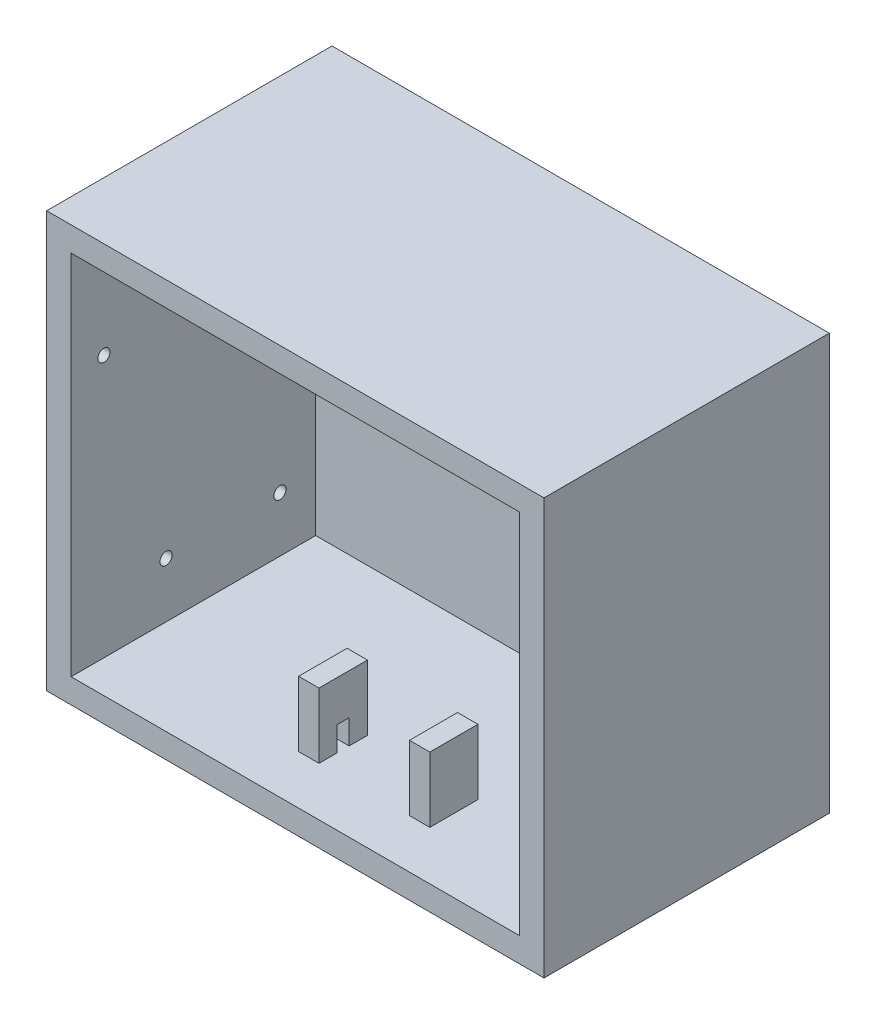
SolidWorks part; units mm, degrees
ref_plane "Front Plane" through (0, 0, 0) normal (0, 0, 1) x (1, 0, 0)
ref_plane "Top Plane" through (0, 0, 0) normal (0, 1, 0) x (1, 0, 0)
ref_plane "Right Plane" through (0, 0, 0) normal (1, 0, 0) x (0, 0, -1)
sketch "Sketch1" plane through (0, 0, 0) normal (0, 0, 1) x (1, 0, 0)
  line L0 (61, 51) -> (-61, 51)
  line L1 (55, -45) -> (-55, -45)
  line L2 (55, -45) -> (55, 45)
  line L3 (55, 45) -> (-55, 45)
  line L4 (-55, -45) -> (-55, 45)
  line L5 (55, -45) -> (-55, 45) construction
  line L6 (55, 45) -> (-55, -45) construction
  line L7 (-61, -51) -> (-61, 51)
  line L8 (61, -51) -> (-61, -51)
  line L9 (61, -51) -> (61, 51)
  point P0 (0, 0)
  dimension "D1" = 90
  dimension "D2" = 110
  dimension "D3" = 6
extrude "Boss-Extrude1" add sketch "Sketch1" along normal blind 70
sketch "Sketch3" plane through (61, 0, 0) normal (1, 0, 0) x (0, 0, -1)
  line L0 (-70, -51) -> (0, -51) construction
  line L1 (0, 51) -> (-10, 51)
  line L2 (0, 51) -> (0, -51)
  line L3 (0, -51) -> (-10, -51)
  line L4 (-10, 51) -> (-10, -51)
  dimension "D1" = 10
extrude "Boss-Extrude3" add sketch "Sketch3" against normal blind 122
sketch "Sketch5" plane through (-61, 0, 0) normal (-1, 0, 0) x (0, 0, 1)
  line L0 (70, 51) -> (0, 51) construction
  line L1 (11.16, 34.5) -> (64.5, 34.5)
  line L2 (11.16, 34.5) -> (11.16, -34.08)
  line L3 (11.16, -34.08) -> (64.5, -34.08)
  line L4 (64.5, 34.5) -> (64.5, -34.08)
  line L5 (70, 51) -> (70, -51) construction
  circle A0 centre (61.96, 19.26) radius 1.5
  circle A1 centre (13.7, 19.26) radius 1.5
  point P4 (37.83, 34.5)
  point P9 (64.5, 19.26)
  point P10 (61.96, 19.26)
  point P11 (13.7, 19.26)
  dimension "D1" = 68.58
  dimension "D2" = 53.34
  dimension "D3" = 16.5
  dimension "D4" = 5.5
  dimension "D5" = 15.24
  dimension "D6" = 2.54
  dimension "D7" = 2.54
sketch "Sketch6" plane through (-61, 0, 0) normal (-1, 0, 0) x (0, 0, 1)
  line L0 (11.16, -34.08) -> (64.5, -34.08) construction
  circle A0 centre (18.78, -31.5) radius 1.5
  circle A1 centre (46.72, -31.5) radius 1.5
  point P0 (18.78, -34.08)
  point P1 (-61.2014, -14.8235)
  point P2 (-50.5223, 20.308)
  point P3 (46.72, -34.08)
  point P5 (18.78, -31.5)
  point P8 (46.72, -31.5)
  dimension "D1" = 7.62
  dimension "D2" = 35.56
  dimension "D3" = 2.58
  dimension "D4" = 2.58
extrude "Cut-Extrude1" cut sketch "Sketch6" against normal blind 10
extrude "Cut-Extrude2" cut sketch "Sketch5" against normal blind 10 contours A0
extrude "Cut-Extrude3" cut sketch "Sketch5<3>" against normal blind 10 contours A1
sketch "Sketch5<3>" plane through (-61, 0, 0) normal (-1, 0, 0) x (0, 0, 1) same geometry as "Sketch5"
sketch "Sketch7" plane through (0, -51, 0) normal (0, -1, 0) x (1, 0, 0)
  line L0 (61, 70) -> (61, 0) construction
  line L1 (16, 58) -> (-6.2, 58)
  line L2 (16, 58) -> (16, 46.2)
  line L3 (16, 46.2) -> (-6.2, 46.2)
  line L4 (-6.2, 58) -> (-6.2, 46.2)
  line L5 (-61, 70) -> (61, 70) construction
  dimension "D1" = 22.2
  dimension "D2" = 11.8
  dimension "D3" = 45
  dimension "D4" = 12
sketch "Sketch8" plane through (0, -51, 0) normal (0, -1, 0) x (1, 0, 0)
  line L1 (16, 58) -> (21, 58)
  line L2 (16, 58) -> (16, 46.2)
  line L3 (16, 46.2) -> (21, 46.2)
  line L4 (21, 58) -> (21, 46.2)
  line L5 (-6.2, 58) -> (-11.2, 58)
  line L6 (-6.2, 58) -> (-6.2, 46.1024)
  line L7 (-6.2, 46.1024) -> (-11.2, 46.1024)
  line L8 (-11.2, 58) -> (-11.2, 46.1024)
  dimension "D1" = 11.8
  dimension "D2" = 5
  dimension "D3" = 5
extrude "Boss-Extrude4" add sketch "Sketch8" against normal blind 22
sketch "Sketch9" plane through (0, -17, 0) normal (0, 1, 0) x (1, 0, 0)
  circle A0 centre (27.7837, -52.0191) radius 1.5
sketch "Sketch10" plane through (0, -17, 0) normal (0, 1, 0) x (1, 0, 0)
  circle A0 centre (2.7148, -51.9014) radius 1.5
extrude "Cut-Extrude4" cut sketch "Sketch9" against normal blind 7 contours A0 rebuild error yes
extrude "Cut-Extrude5" cut sketch "Sketch10" against normal blind 7 contours A0 rebuild error yes
sketch "Sketch14" plane through (-11.2, 0, 0) normal (-1, 0, 0) x (0, 0, 1)
  line L1 (53.6, -45) -> (50.6, -45)
  line L2 (53.6, -45) -> (53.6, -39)
  line L3 (53.6, -39) -> (50.6, -39)
  line L4 (50.6, -45) -> (50.6, -39)
  dimension "D1" = 6
  dimension "D2" = 3
  dimension "D3" = 4.4
extrude "Cut-Extrude6" cut sketch "Sketch14" against normal blind 10
